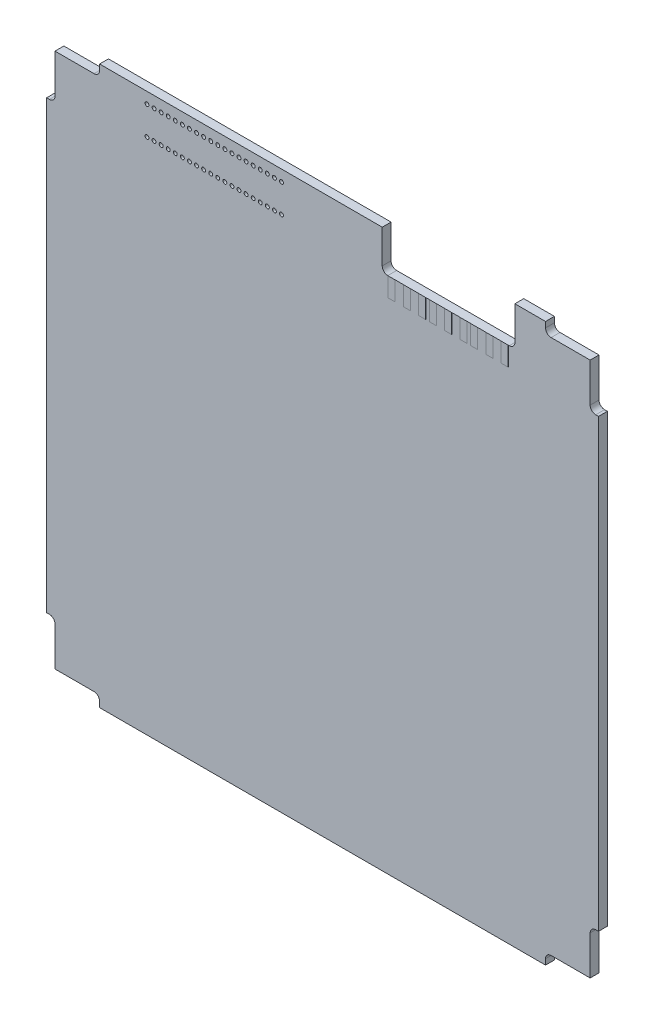
SolidWorks part; units mm, degrees
material "ABS"
ref_plane "Front Plane" through (0, 0, 0) normal (0, 0, 1) x (1, 0, 0)
ref_plane "Top Plane" through (0, 0, 0) normal (0, 1, 0) x (1, 0, 0)
ref_plane "Right Plane" through (0, 0, 0) normal (1, 0, 0) x (0, 0, -1)
sketch "Sketch1" plane through (0, 0, 0) normal (0, 0, 1) x (1, 0, 0)
  line L0 (-40, 50) -> (-40, 48)
  line L1 (-50, -50) -> (50, -50)
  line L2 (-50, -50) -> (-50, 50)
  line L3 (-50, 50) -> (50, 50)
  line L4 (50, -50) -> (50, 50)
  line L5 (-50, -50) -> (50, 50) construction
  line L6 (-50, 50) -> (50, -50) construction
  line L7 (-50, 50) -> (-40, 50)
  line L8 (-50, 50) -> (-50, 40)
  line L9 (-40, 48) -> (-48, 48)
  line L10 (-48, 48) -> (-48, 40)
  line L11 (50, 50) -> (40, 50)
  line L12 (50, 50) -> (50, 40)
  line L13 (-48, 40) -> (-50, 40)
  line L14 (50, 40) -> (48, 40)
  line L15 (-50, -50) -> (-37.8649, -50)
  line L16 (-50, -50) -> (-50, -37.8649)
  line L17 (50, 50) -> (50, 40)
  line L18 (50, 50) -> (40, 50)
  line L19 (50, -50) -> (41.5, -50)
  line L20 (50, -50) -> (50, -41.5)
  line L21 (48, 40) -> (48, 48)
  line L22 (48, 48) -> (40, 48)
  line L23 (40, 48) -> (40, 50)
  line L24 (40, -50) -> (40, -48)
  line L25 (50, -50) -> (40, -50)
  line L26 (50, -50) -> (50, -40)
  line L27 (40, -48) -> (48, -48)
  line L28 (48, -48) -> (48, -40)
  line L29 (48, -40) -> (50, -40)
  line L30 (-50, -40) -> (-48, -40)
  line L31 (-50, -50) -> (-50, -40)
  line L32 (-50, -50) -> (-40, -50)
  line L33 (-48, -40) -> (-48, -48)
  line L34 (-48, -48) -> (-40, -48)
  line L35 (-40, -48) -> (-40, -50)
  point P0 (0, 0)
  point P38 (0, 0)
  dimension "D1" = 100
  dimension "D2" = 100
  dimension "D3" = 2
  dimension "D4" = 10
  dimension "D5" = 4
extrude "Boss-Extrude1" add sketch "Sketch1" along normal blind 1.5875 contours L1 L4 L3 L2 region at (0, 0, 0)
fillet "Fillet1" radius 1 8 edges at (-48, -40, 0.7937) (-40, -48, 0.7937) (40, -48, 0.7937) (48, -40, 0.7937) (48, 40, 0.7937) (40, 48, 0.7937) (-40, 48, 0.7937) (-48, 40, 0.7937)
sketch "Sketch2" plane through (0, 0, 1.5875) normal (0, 0, 1) x (1, 0, 0)
  line L0 (0, 50) -> (0, -50) construction
  line L1 (-40, 50) -> (40, 50) construction
  line L2 (-40, -50) -> (40, -50) construction
  line L3 (-50, -40) -> (-50, 40) construction
  line L4 (-40, 50) -> (40, 50) construction
  circle A0 centre (-31.5, 48) radius 0.35
  circle A1 centre (-30.23, 48) radius 0.35
  circle A2 centre (-28.96, 48) radius 0.35
  circle A3 centre (-27.69, 48) radius 0.35
  circle A4 centre (-26.42, 48) radius 0.35
  circle A5 centre (-25.15, 48) radius 0.35
  circle A6 centre (-23.88, 48) radius 0.35
  circle A7 centre (-22.61, 48) radius 0.35
  circle A8 centre (-21.34, 48) radius 0.35
  circle A9 centre (-20.07, 48) radius 0.35
  circle A10 centre (-18.8, 48) radius 0.35
  circle A11 centre (-17.53, 48) radius 0.35
  circle A12 centre (-16.26, 48) radius 0.35
  circle A13 centre (-14.99, 48) radius 0.35
  circle A14 centre (-13.72, 48) radius 0.35
  circle A15 centre (-12.45, 48) radius 0.35
  circle A16 centre (-11.18, 48) radius 0.35
  circle A17 centre (-9.91, 48) radius 0.35
  circle A18 centre (-8.64, 48) radius 0.35
  circle A19 centre (-7.37, 48) radius 0.35
  circle A20 centre (-30.23, 42.92) radius 0.35
  circle A21 centre (-28.96, 42.92) radius 0.35
  circle A22 centre (-27.69, 42.92) radius 0.35
  circle A23 centre (-26.42, 42.92) radius 0.35
  circle A24 centre (-25.15, 42.92) radius 0.35
  circle A25 centre (-23.88, 42.92) radius 0.35
  circle A26 centre (-22.61, 42.92) radius 0.35
  circle A27 centre (-21.34, 42.92) radius 0.35
  circle A28 centre (-20.07, 42.92) radius 0.35
  circle A29 centre (-18.8, 42.92) radius 0.35
  circle A30 centre (-17.53, 42.92) radius 0.35
  circle A31 centre (-16.26, 42.92) radius 0.35
  circle A32 centre (-14.99, 42.92) radius 0.35
  circle A33 centre (-13.72, 42.92) radius 0.35
  circle A34 centre (-12.45, 42.92) radius 0.35
  circle A35 centre (-11.18, 42.92) radius 0.35
  circle A36 centre (-9.91, 42.92) radius 0.35
  circle A37 centre (-8.64, 42.92) radius 0.35
  circle A38 centre (-7.37, 42.92) radius 0.35
  circle A39 centre (-31.5, 42.92) radius 0.35
  dimension "D1" = 0.7
  dimension "D4" = 18.5
  dimension "D5" = 2
  dimension "D2" = 5.08
  dimension "D3" = 1.27
extrude "Cut-Extrude1" cut sketch "Sketch2" against normal through all
sketch "Sketch3" plane through (0, 50, 0) normal (0, 1, 0) x (1, 0, 0)
  line L0 (-40, 0) -> (40, 0) construction
  line L1 (10.7, 0) -> (19.7, 0)
  line L2 (10.7, 0) -> (10.7, -1.5875)
  line L3 (10.7, -1.5875) -> (19.7, -1.5875)
  line L4 (-40, -1.5875) -> (-40, 0) construction
  line L5 (-40, -1.5875) -> (40, -1.5875) construction
  line L6 (15.2, 0) -> (15.2, -1.5875) construction
  line L7 (12, 0) -> (12, -1.5875) construction
  line L8 (18.4, 0) -> (18.4, -1.5875) construction
  line L9 (-40, -1.5875) -> (40, -1.5875) construction
  line L12 (19.7, 0) -> (34.5, 0)
  line L14 (19.7, -1.5875) -> (34.5, -1.5875)
  line L15 (34.5, 0) -> (34.5, -1.5875)
  dimension "D1" = 9
  dimension "D2" = 6.4
  dimension "D3" = 3.2
  dimension "D5" = 14.8
  dimension "D6" = 50.7
extrude "Cut-Extrude2" cut sketch "Sketch3" against normal blind 7.0216
fillet "Fillet2" radius 1 2 edges at (10.7, 42.9784, 0.7938) (34.5, 42.9784, 0.7937)
sketch "Sketch5" plane through (0, 0, 0) normal (0, 0, -1) x (-1, 0, 0)
  line L0 (40, -50) -> (-40, -50) construction
  line L1 (-49.5, 50) -> (49.5, 50)
  line L2 (-49.5, 50) -> (-49.5, -50)
  line L3 (-49.5, -50) -> (49.5, -50)
  line L4 (49.5, 50) -> (49.5, -50)
  line L5 (40, 50) -> (-10.7, 50) construction
  line L6 (50, -40) -> (50, 40) construction
  dimension "D1" = 99
  dimension "D2" = 0.5
extrude "Cut-Extrude3" cut sketch "Sketch5" against normal through all flip side to cut
sketch "Sketch6" plane through (0, 0, 1.5875) normal (0, 0, 1) x (1, 0, 0)
  line L0 (12.4, 42.9784) -> (12.4, 39.5484) construction
  line L1 (11.765, 42.9784) -> (13.035, 42.9784)
  line L2 (11.765, 42.9784) -> (11.765, 39.5484)
  line L3 (11.765, 39.5484) -> (13.035, 39.5484)
  line L4 (13.035, 42.9784) -> (13.035, 39.5484)
  line L5 (14.505, 42.9784) -> (15.775, 42.9784)
  line L6 (14.505, 42.9784) -> (14.505, 39.5484)
  line L7 (14.505, 39.5484) -> (15.775, 39.5484)
  line L8 (15.775, 42.9784) -> (15.775, 39.5484)
  line L9 (17.245, 42.9784) -> (18.515, 42.9784)
  line L10 (17.245, 42.9784) -> (17.245, 39.5484)
  line L11 (17.245, 39.5484) -> (18.515, 39.5484)
  line L12 (18.515, 42.9784) -> (18.515, 39.5484)
  line L13 (15.14, 42.9784) -> (15.14, 39.5484) construction
  line L14 (17.88, 42.9784) -> (17.88, 39.5484) construction
  line L15 (11.7, 42.9784) -> (33.5, 42.9784) construction
  line L16 (12.8, 39.7784) -> (12, 39.7784) construction
  line L17 (19.165, 42.9784) -> (20.435, 42.9784)
  line L18 (19.165, 42.9784) -> (19.165, 39.5484)
  line L19 (19.165, 39.5484) -> (20.435, 39.5484)
  line L20 (20.435, 42.9784) -> (20.435, 39.5484)
  line L21 (21.905, 42.9784) -> (23.175, 42.9784)
  line L22 (21.905, 42.9784) -> (21.905, 39.5484)
  line L23 (21.905, 39.5484) -> (23.175, 39.5484)
  line L24 (23.175, 42.9784) -> (23.175, 39.5484)
  line L25 (24.645, 42.9784) -> (25.915, 42.9784)
  line L26 (24.645, 42.9784) -> (24.645, 39.5484)
  line L27 (24.645, 39.5484) -> (25.915, 39.5484)
  line L28 (25.915, 42.9784) -> (25.915, 39.5484)
  line L29 (19.8, 42.9784) -> (19.8, 39.5484) construction
  line L30 (22.54, 42.9784) -> (22.54, 39.5484) construction
  line L31 (25.28, 42.9784) -> (25.28, 39.5484) construction
  line L32 (26.565, 42.9784) -> (27.835, 42.9784)
  line L33 (26.565, 42.9784) -> (26.565, 39.5484)
  line L34 (26.565, 39.5484) -> (27.835, 39.5484)
  line L35 (27.835, 42.9784) -> (27.835, 39.5484)
  line L36 (29.305, 42.9784) -> (30.575, 42.9784)
  line L37 (29.305, 42.9784) -> (29.305, 39.5484)
  line L38 (29.305, 39.5484) -> (30.575, 39.5484)
  line L39 (30.575, 42.9784) -> (30.575, 39.5484)
  line L40 (32.045, 42.9784) -> (33.315, 42.9784)
  line L41 (32.045, 42.9784) -> (32.045, 39.5484)
  line L42 (32.045, 39.5484) -> (33.315, 39.5484)
  line L43 (33.315, 42.9784) -> (33.315, 39.5484)
  line L44 (27.2, 42.9784) -> (27.2, 39.5484) construction
  line L45 (29.94, 42.9784) -> (29.94, 39.5484) construction
  line L46 (32.68, 42.9784) -> (32.68, 39.5484) construction
  point P20 (12.4, 39.7784)
  point P42 (19.8, 39.7784)
  point P61 (27.2, 39.7784)
  dimension "D1" = 1.27
  dimension "D2" = 3.43
  dimension "D3" = 2.74
  dimension "D4" = 2.74
  dimension "D6" = 7.4
  dimension "D5" = 3
extrude "Boss-Extrude2" add sketch "Sketch6" along normal blind 0.01
sketch "Sketch7" plane through (0, 0, 1.5875) normal (0, 0, 1) x (1, 0, 0)
  line L0 (-40, 50) -> (-36.5, 50)
  line L1 (-40, 50) -> (10.7, 50) construction
  line L2 (-36.5, 50) -> (-36.5, 48)
  line L3 (-36.5, 48) -> (-41.5, 48)
  line L4 (-41, 48) -> (-48, 48) construction
  line L5 (-41.5, 48) -> (-41.5, 41.5)
  line L6 (-41.5, 41.5) -> (-42, 41.5)
  line L7 (-47, 36.5) -> (-47, -36.5)
  line L8 (-40, 50) -> (-49.5, 50)
  line L9 (-49.5, 50) -> (-49.5, -50)
  line L10 (-49.5, -40) -> (-49.5, 40) construction
  line L11 (0, 0) -> (-49.5, 0) construction
  line L12 (-40, -50) -> (-49.5, -50)
  line L13 (-41.5, -41.5) -> (-42, -41.5)
  line L14 (-41.5, -48) -> (-41.5, -41.5)
  line L15 (-36.5, -48) -> (-41.5, -48)
  line L16 (-36.5, -50) -> (-36.5, -48)
  line L17 (-40, -50) -> (-36.5, -50)
  arc A0 (-42, 41.5) -> (-47, 36.5) centre (-42, 36.5) ccw
  arc A1 (-42, -41.5) -> (-47, -36.5) centre (-42, -36.5) cw
  point P25 (-47, 0)
  dimension "D1" = 5
  dimension "D2" = 13
  dimension "D3" = 8
  dimension "D4" = 8.5
  dimension "D5" = 2.5
  dimension "D6" = 5
